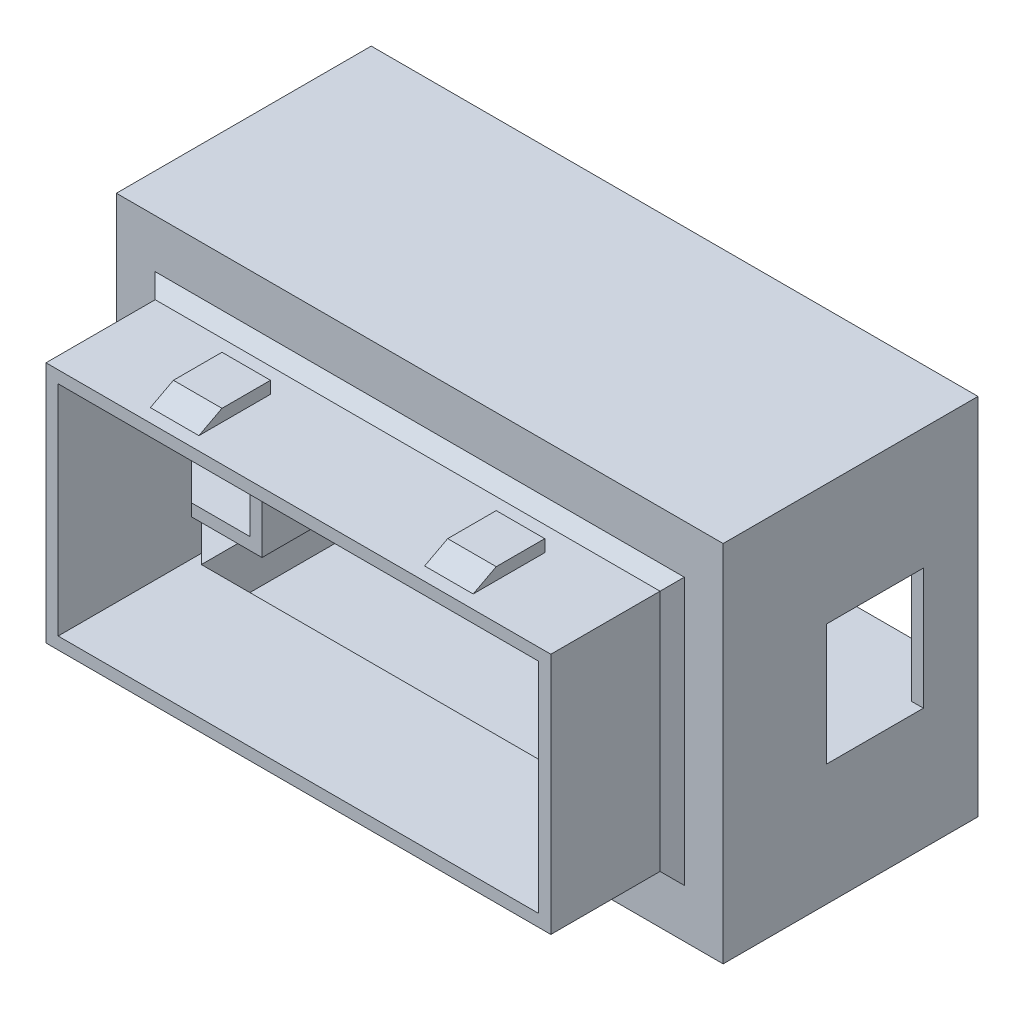
SolidWorks part; units mm, degrees
ref_plane "Front Plane" through (0, 0, 0) normal (0, 0, 1) x (1, 0, 0)
ref_plane "Top Plane" through (0, 0, 0) normal (0, 1, 0) x (1, 0, 0)
ref_plane "Right Plane" through (0, 0, 0) normal (1, 0, 0) x (0, 0, -1)
sketch "Sketch1" plane through (0, 0, 0) normal (0, 0, 1) x (1, 0, 0)
  line L0 (19.8, 9) -> (19.8, -9)
  line L1 (-20.8, 10) -> (20.8, 10)
  line L2 (-20.8, 10) -> (-20.8, -10)
  line L3 (-20.8, -10) -> (20.8, -10)
  line L4 (20.8, 10) -> (20.8, -10)
  line L5 (-20.8, 10) -> (20.8, -10) construction
  line L6 (-20.8, -10) -> (20.8, 10) construction
  line L7 (-19.8, -9) -> (19.8, -9)
  line L8 (-19.8, 9) -> (-19.8, -9)
  line L9 (-19.8, 9) -> (19.8, 9)
  point P0 (0, 0)
  dimension "D1" = 1
extrude "Boss-Extrude2" add sketch "Sketch1" along normal blind 10
sketch "Sketch2" plane through (0, -10, 0) normal (0, -1, 0) x (1, 0, 0)
  line L0 (0, 10) -> (0, 0)
  line L1 (-20.8, 10) -> (20.8, 10) construction
  line L3 (-9.3, 10) -> (9.3, 10)
  line L4 (-9.3, 10) -> (-9.3, 0)
  line L5 (-9.3, 0) -> (9.3, 0)
  line L6 (9.3, 10) -> (9.3, 0)
  line L7 (-9.3, 10) -> (9.3, 0) construction
  line L8 (-9.3, 0) -> (9.3, 10) construction
  line L9 (9.3, 10) -> (13.3, 10)
  line L10 (9.3, 10) -> (9.3, 0)
  line L11 (9.3, 0) -> (13.3, 0)
  line L12 (13.3, 10) -> (13.3, 0)
  line L13 (-9.3, 10) -> (-13.3, 10)
  line L14 (-9.3, 10) -> (-9.3, 0)
  line L15 (-9.3, 0) -> (-13.3, 0)
  line L16 (-13.3, 10) -> (-13.3, 0)
  point P5 (0, 5)
  line M1 (-20.8, 0) -> (20.8, 0)
  line M3 (20.8, 10) -> (-20.8, 10)
extrude "Boss-Extrude3" add sketch "Sketch2" along normal blind 1 contours L16 L4 M3 M1 | L12 L6 M3 M1
sketch "Sketch3" plane through (-13.3, 0, 0) normal (-1, 0, 0) x (0, 0, 1)
  line L0 (7, -11) -> (8.9001, -10)
  line L1 (10, -11) -> (7, -11)
  line L2 (10, -11) -> (10, -10)
  line L3 (10, -10) -> (7, -10)
  line L4 (7, -11) -> (7, -10)
  line L5 (0, -11) -> (0, -10) construction
  line L6 (7, -10) -> (3, -10)
  line L7 (7, -10) -> (7, -11)
  line L8 (7, -11) -> (3, -11)
  line L9 (3, -10) -> (3, -11)
  line L10 (3, -10) -> (0, -10)
  line L11 (3, -10) -> (3, -11)
  line L12 (3, -11) -> (0, -11)
  line L13 (0, -10) -> (0, -11)
  line L14 (10, -11) -> (0, -11) construction
  line M1 (10, -10) -> (0, -10)
  line M2 (0, -10) -> (0, -11)
  line M3 (0, -11) -> (10, -11)
  line M4 (10, -11) -> (10, -10)
extrude "Cut-Extrude1" cut sketch "Sketch3" against normal blind 27 contours L0 M3 M4 M1 | L9 M1 M2 M3
sketch "Sketch4" plane through (0, 10, 0) normal (0, 1, 0) x (1, 0, 0)
  line L0 (0, -10) -> (0, 0)
  line L1 (20.8, -10) -> (-20.8, -10) construction
  line L2 (20.8, 0) -> (-20.8, 0) construction
  line L4 (9.3, -10) -> (-9.3, -10)
  line L5 (9.3, -10) -> (9.3, 0)
  line L6 (9.3, 0) -> (-9.3, 0)
  line L7 (-9.3, -10) -> (-9.3, 0)
  line L8 (9.3, -10) -> (-9.3, 0) construction
  line L9 (9.3, 0) -> (-9.3, -10) construction
  line L10 (-9.3, -10) -> (-13.3, -10)
  line L11 (-9.3, -10) -> (-9.3, 0)
  line L12 (-9.3, 0) -> (-13.3, 0)
  line L13 (-13.3, -10) -> (-13.3, 0)
  line L14 (9.3, -10) -> (13.3, -10)
  line L15 (9.3, -10) -> (9.3, 0)
  line L16 (9.3, 0) -> (13.3, 0)
  line L17 (13.3, -10) -> (13.3, 0)
  point P6 (0, -5)
  line M1 (20.8, 0) -> (-20.8, 0)
  line M3 (-20.8, -10) -> (20.8, -10)
extrude "Boss-Extrude4" add sketch "Sketch4" along normal blind 1 contours L17 L5 M3 M1 | L13 L7 M3 M1
sketch "Sketch5" plane through (13.3, 0, 0) normal (1, 0, 0) x (0, 0, -1)
  line L1 (-10, 11) -> (0, 11) construction
  line L2 (-10, 10) -> (0, 10) construction
  line L3 (-10, 11) -> (-7, 11)
  line L4 (-10, 11) -> (-10, 10)
  line L5 (-10, 10) -> (-7, 10)
  line L6 (-7, 11) -> (-7, 10)
  line L7 (-10, 10) -> (0, 10) construction
  line L8 (-7, 11) -> (-3, 11)
  line L9 (-7, 11) -> (-7, 10)
  line L10 (-7, 10) -> (-3, 10)
  line L11 (-3, 11) -> (-3, 10)
  line L12 (-7, 11) -> (-8.9001, 10)
  line M1 (-10, 10) -> (0, 10)
  line M2 (0, 10) -> (0, 11)
  line M3 (0, 11) -> (-10, 11)
  line M4 (-10, 11) -> (-10, 10)
extrude "Cut-Extrude2" cut sketch "Sketch5" against normal blind 27 contours L12 M3 M4 M1 | L11 M3 M1 M2
sketch "Sketch6" plane through (0, 0, 0) normal (0, 0, -1) x (-1, 0, 0)
  line L0 (19.8, -9) -> (-19.8, -9) construction
  line L1 (-20.8, 10) -> (20.8, 10)
  line L2 (-20.8, 10) -> (-20.8, -10)
  line L3 (-20.8, -10) -> (20.8, -10)
  line L4 (20.8, 10) -> (20.8, -10)
  line L5 (-20.8, 10) -> (20.8, -10) construction
  line L6 (-20.8, -10) -> (20.8, 10) construction
  line L7 (-19.8, 9) -> (19.8, 9)
  line L8 (-19.8, 9) -> (-19.8, -9)
  line L9 (-19.8, -9) -> (19.8, -9)
  line L10 (19.8, 9) -> (19.8, -9)
  line L11 (-19.8, 9) -> (19.8, -9) construction
  line L12 (-19.8, -9) -> (19.8, 9) construction
  line L14 (-25, 15) -> (25, 15)
  line L15 (-25, 15) -> (-25, -15)
  line L16 (-25, -15) -> (25, -15)
  line L17 (25, 15) -> (25, -15)
  line L18 (-25, 15) -> (25, -15) construction
  line L19 (-25, -15) -> (25, 15) construction
  point P0 (0, 0)
  point P7 (0, 0)
  point P14 (0, 0)
  line M1 (20.8, -10) -> (20.8, 10)
  line M2 (20.8, 10) -> (-20.8, 10)
  line M3 (-20.8, 10) -> (-20.8, -10)
  line M4 (-20.8, -10) -> (20.8, -10)
  line M5 (-19.8, 9) -> (19.8, 9)
  line M6 (19.8, 9) -> (19.8, -9)
  line M7 (19.8, -9) -> (-19.8, -9)
  line M8 (-19.8, -9) -> (-19.8, 9)
extrude "Boss-Extrude6" add sketch "Sketch6" along normal blind 1 contours M4 M1 M2 M3 M8 M5 M6 M7 | L17 L14 L15 L16 M1 M4 M3 M2
chamfer "Chamfer1" distance 1 angle 45 4 edges at (-20.8, 0, 0) (20.8, 0, 0)
sketch "Sketch7" plane through (0, 0, -1) normal (0, 0, -1) x (-1, 0, 0)
  line L0 (-25, 15) -> (25, 15)
  line L1 (-24, 14) -> (24, 14)
  line L2 (-24, 14) -> (-24, -14)
  line L3 (-24, -14) -> (24, -14)
  line L4 (24, 14) -> (24, -14)
  line L5 (-24, 14) -> (24, -14) construction
  line L6 (-24, -14) -> (24, 14) construction
  line L7 (25, 15) -> (25, -15)
  line L8 (-25, -15) -> (25, -15)
  line L9 (-25, 15) -> (-25, -15)
  point P0 (0, 0)
  dimension "D1" = 1
extrude "Boss-Extrude7" add sketch "Sketch7" along normal blind 20
sketch "Sketch8" plane through (0, 0, -1) normal (0, 0, -1) x (-1, 0, 0)
  line L0 (-19.8, 0) -> (-24, 0)
  line L1 (-19.8, -9) -> (-19.8, 9) construction
  line L2 (-24, 14) -> (-24, -14) construction
  line L3 (-24, 0) -> (-24, 5)
  line L4 (-24, 0) -> (-24, -5)
  line L5 (-24, 6) -> (-14, 6)
  line L6 (-24, 5) -> (-15, 5)
  line L7 (-24, 5) -> (-24, -5)
  line L8 (-24, -5) -> (-15, -5)
  line L9 (-15, 5) -> (-15, -5)
  line L10 (-14, 6) -> (-14, -6)
  line L11 (-24, -6) -> (-14, -6)
  line M3 (-24, 14) -> (-24, -14)
  line M5 (-19.8, -9) -> (-19.8, 9)
  dimension "D1" = 1
extrude "Boss-Extrude8" add sketch "Sketch8" along normal blind 20 contours L11 L10 L5 L6 L9 L8 M5 | L6 L5 M3 M5 | L11 L8 M3 M5
sketch "Sketch9" plane through (0, 0, -1) normal (0, 0, -1) x (-1, 0, 0)
  line L0 (19.8, 0) -> (24, 0)
  line L1 (19.8, 9) -> (19.8, -9) construction
  line L2 (24, -14) -> (24, 14) construction
  line L3 (24, 0) -> (24, -5)
  line L4 (24, 0) -> (24, 5)
  line L5 (24, 6) -> (14, 6)
  line L6 (24, 5) -> (15, 5)
  line L7 (24, 5) -> (24, -5)
  line L8 (24, -5) -> (15, -5)
  line L9 (15, 5) -> (15, -5)
  line L10 (14, 6) -> (14, -6)
  line L11 (24, -6) -> (14, -6)
  line M5 (24, -14) -> (24, 14)
  line M11 (19.8, 9) -> (19.8, -9)
  dimension "D1" = 1
extrude "Boss-Extrude9" add sketch "Sketch9" along normal blind 20 contours L11 L8 L9 L6 L5 L10 M11 | L6 L5 M5 M11 | L11 L8 M5 M11
sketch "Sketch10" plane through (0, 0, -1) normal (0, 0, -1) x (-1, 0, 0)
  line L0 (-24, -6) -> (-24, -14) construction
  line L1 (-24, 14) -> (-20, 14)
  line L2 (-24, 14) -> (-24, 10)
  line L3 (-24, 10) -> (-20, 10)
  line L4 (-20, 14) -> (-20, 10)
  line L5 (24, 14) -> (20, 14)
  line L6 (24, 14) -> (24, 10)
  line L7 (24, 10) -> (20, 10)
  line L8 (20, 14) -> (20, 10)
  line L9 (24, -14) -> (20, -14)
  line L10 (24, -14) -> (24, -10)
  line L11 (24, -10) -> (20, -10)
  line L12 (20, -14) -> (20, -10)
  line L13 (-24, -14) -> (-20, -14)
  line L14 (-24, -14) -> (-24, -10)
  line L15 (-24, -10) -> (-20, -10)
  line L16 (-20, -14) -> (-20, -10)
extrude "Boss-Extrude10" add sketch "Sketch10" along normal blind 20
sketch "Sketch11" plane through (-25, 0, 0) normal (-1, 0, 0) x (0, 0, 1)
  line L0 (-10.5, 15) -> (-10.5, -15)
  line L1 (-21, 15) -> (0, 15) construction
  line L2 (-21, -15) -> (0, -15) construction
  line L3 (-16.5, 0) -> (-16.5, 5)
  line L4 (-21, -15) -> (-21, 15) construction
  line L5 (-21, 0) -> (-16.5, 0)
  line L6 (-16.5, 0) -> (-16.5, -5)
  line L8 (-16.5, 5) -> (-8.5, 5)
  line L9 (-16.5, 5) -> (-16.5, -5)
  line L10 (-16.5, -5) -> (-8.5, -5)
  line L11 (-8.5, 5) -> (-8.5, -5)
extrude "Cut-Extrude3" cut sketch "Sketch11" against normal blind 1 contours L6 L10 L0 L8 L3 | L11 L8 L0 L10
sketch "Sketch12" plane through (25, 0, 0) normal (1, 0, 0) x (0, 0, -1)
  line L0 (10.5, 15) -> (10.5, -15)
  line L1 (21, 15) -> (0, 15) construction
  line L2 (21, -15) -> (0, -15) construction
  line L3 (16.5, 0) -> (16.5, 5)
  line L4 (21, 15) -> (21, -15) construction
  line L5 (21, 0) -> (16.5, 0)
  line L6 (16.5, 0) -> (16.5, -5)
  line L8 (16.5, -5) -> (8.5, -5)
  line L9 (16.5, -5) -> (16.5, 5)
  line L10 (16.5, 5) -> (8.5, 5)
  line L11 (8.5, -5) -> (8.5, 5)
extrude "Cut-Extrude4" cut sketch "Sketch12" against normal blind 1 contours L11 L8 L0 L10 | L3 L10 L0 L8 L6
sketch "Sketch13" plane through (0, 0, -21) normal (0, 0, -1) x (-1, 0, 0)
  line L0 (-20, 10) -> (-25, 15)
  line L1 (20, 10) -> (25, 15)
  line L2 (-20, -10) -> (-25, -15)
  line L3 (-25, 15) -> (-25, -15) construction
  line L4 (-25, -15) -> (25, -15) construction
  line L5 (20, -10) -> (25, -15)
  circle A0 centre (-22.5, 12.5) radius 1.5
  circle A1 centre (22.5, 12.5) radius 1.5
  circle A2 centre (22.5, -12.5) radius 1.5
  circle A3 centre (-22.5, -12.5) radius 1.5
extrude "Cut-Extrude5" cut sketch "Sketch13" against normal blind 10 contours A0 | A1 | A2 | A3
chamfer "Chamfer2" distance 5 angle 45 10 edges at (22, 10, -1) (20, 12, -1) (0, 14, -1) (-20, 12, -1) (-22, 10, -1) (-22, -10, -1) (-20, -12, -1) (0, -14, -1) (20, -12, -1) (22, -10, -1)
chamfer "Chamfer3" distance 5 angle 45 20 edges at (19.8, -7.5, -1) (-19.8, 7.5, -1) (24, -7.5, -1) (19.8, 7.5, -1) (21.9, 6, -1) (21.9, -6, -1) (-24, 7.5, -1) (-19.8, -7.5, -1) (-21.9, -6, -1) (-21.9, 6, -1) (-24, -7.5, -1) (-24, -9.5, -1.5) (-22, -10, -2) (22, -10, -2) (24, -9.5, -1.5) (24, 7.5, -1) (24, 9.5, -1.5) (22, 10, -2) (-22, 10, -2) (-24, 9.5, -1.5)
chamfer "Chamfer4" distance 4 angle 45 2 edges at (24, 0, -1) (-24, 0, -1)
